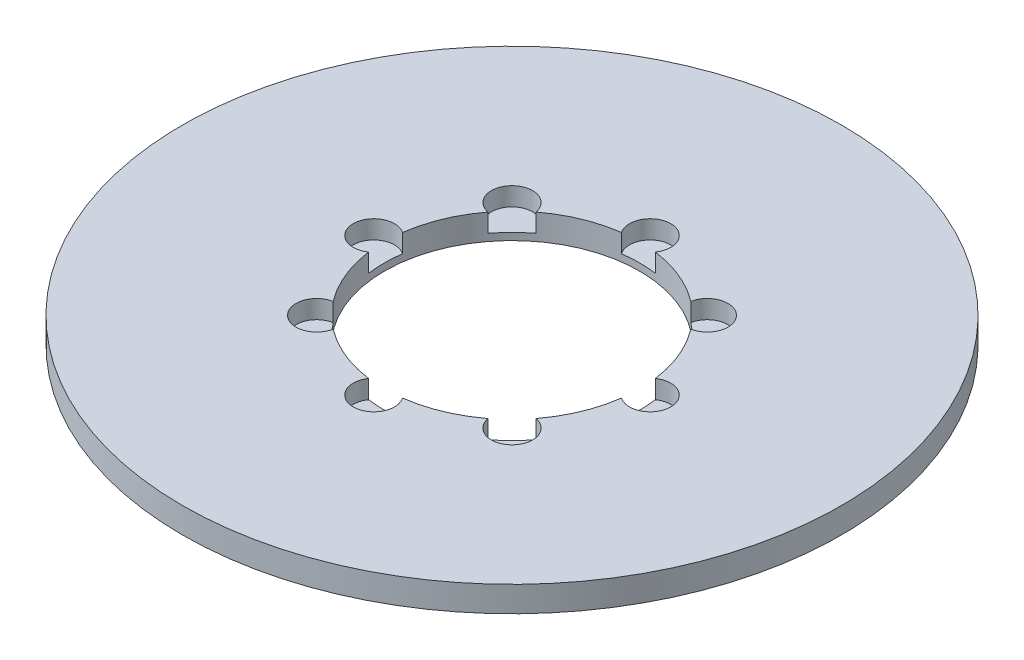
SolidWorks part; units mm, degrees
ref_plane "Front Plane" through (0, 0, 0) normal (0, 0, 1) x (1, 0, 0)
ref_plane "Top Plane" through (0, 0, 0) normal (0, 1, 0) x (1, 0, 0)
ref_plane "Right Plane" through (0, 0, 0) normal (1, 0, 0) x (0, 0, -1)
sketch "Sketch1" plane through (0, 0, 0) normal (0, 1, 0) x (1, 0, 0)
  circle A0 centre (0, 0) radius 77.5
  dimension "FLANGE_OD" = 155
extrude "Boss-Extrude1" add sketch "Sketch1" along normal blind 6
sketch "Sketch2" plane through (0, 0, 0) normal (0, 1, 0) x (1, 0, 0)
  circle A0 centre (0, 0) radius 30
  dimension "BORE_D" = 60
extrude "Cut-Extrude1" cut sketch "Sketch2" along normal through all
sketch "Sketch3" plane through (0, 6, 0) normal (0, 1, 0) x (1, 0, 0)
  circle A0 centre (0, 0) radius 32.4844 construction
  circle A1 centre (-32.4844, 0) radius 4.8443
  dimension "BOLT_D" = 9.6886
  dimension "BOLT_PCD" = 64.9687
extrude "Cut-Extrude2" cut sketch "Sketch3" against normal blind 4.3256
pattern_circular "CirPattern1" count 8 over 360 about axis through (0, 0, 0) along (0, 1, 0) of "Cut-Extrude2"
